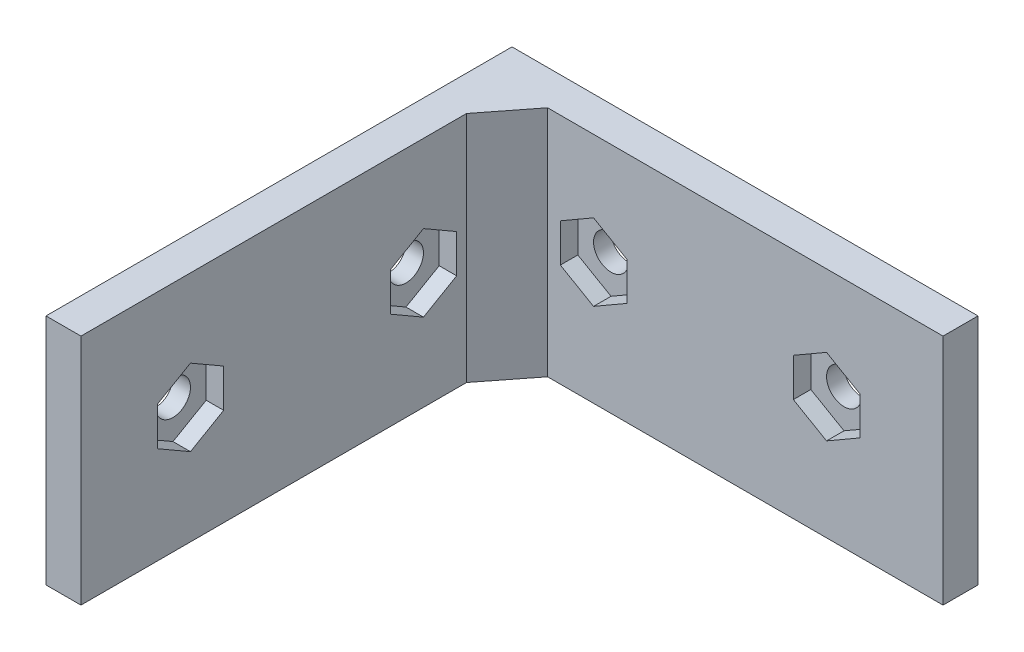
SolidWorks part; units mm, degrees
ref_plane "Plan de face" through (0, 0, 0) normal (0, 0, 1) x (1, 0, 0)
ref_plane "Plan de dessus" through (0, 0, 0) normal (0, 1, 0) x (1, 0, 0)
ref_plane "Plan de droite" through (0, 0, 0) normal (1, 0, 0) x (0, 0, -1)
sketch "Esquisse1" plane through (0, 0, 0) normal (0, 0, 1) x (1, 0, 0)
  line L1 (0, 0) -> (40, 0)
  line L2 (0, 0) -> (0, 20)
  line L3 (0, 20) -> (40, 20)
  line L4 (40, 0) -> (40, 20)
  dimension "D1" = 20
  dimension "D2" = 40
extrude "Boss.-Extru.1" add sketch "Esquisse1" along normal blind 3
sketch "Esquisse2" plane through (0, 0, 3) normal (0, 0, 1) x (1, 0, 0)
  line L0 (0, 20) -> (0, 0) construction
  line L1 (0, 0) -> (40, 0) construction
  circle A0 centre (10, 10.5) radius 1.5
  circle A1 centre (30, 10.5) radius 1.5
  dimension "D1" = 3
  dimension "D2" = 3
  dimension "D4" = 20
  dimension "D5" = 10.5
  dimension "D6" = 10.5
  dimension "D3" = 10
extrude "Enlèv. mat.-Extru.1" cut sketch "Esquisse2" against normal blind 3
sketch "Esquisse3" plane through (0, 0, 3) normal (0, 0, 1) x (1, 0, 0)
  line L0 (0, 0) -> (40, 0) construction
  line L1 (0, 20) -> (3, 20)
  line L2 (0, 20) -> (0, 0)
  line L3 (0, 0) -> (3, 0)
  line L4 (3, 20) -> (3, 0)
  dimension "D1" = 3
extrude "Boss.-Extru.2" add sketch "Esquisse3" along normal blind 37
sketch "Esquisse4" plane through (0, 0, 0) normal (-1, 0, 0) x (0, 0, 1)
  line L0 (0, 20) -> (0, 0) construction
  line L1 (40, 0) -> (0, 0) construction
  circle A0 centre (10.6, 10) radius 1.5
  circle A1 centre (30.6, 10) radius 1.5
  dimension "D1" = 3
  dimension "D2" = 3
  dimension "D3" = 20
  dimension "D4" = 10.6
  dimension "D5" = 10
  dimension "D6" = 10
extrude "Enlèv. mat.-Extru.2" cut sketch "Esquisse4" against normal blind 3
sketch "Esquisse5" plane through (3, 0, 0) normal (1, 0, 0) x (0, 0, -1)
  line L1 (-13.45, 8.3546) -> (-10.6, 6.7091)
  line L2 (-10.6, 6.7091) -> (-7.75, 8.3546)
  line L3 (-7.75, 8.3546) -> (-7.75, 11.6454)
  line L4 (-7.75, 11.6454) -> (-10.6, 13.2909)
  line L5 (-10.6, 13.2909) -> (-13.45, 11.6454)
  line L6 (-13.45, 11.6454) -> (-13.45, 8.3546)
  line L7 (-30.6, 6.7091) -> (-27.75, 8.3546)
  line L8 (-27.75, 8.3546) -> (-27.75, 11.6454)
  line L9 (-27.75, 11.6454) -> (-30.6, 13.2909)
  line L10 (-30.6, 13.2909) -> (-33.45, 11.6454)
  line L11 (-33.45, 11.6454) -> (-33.45, 8.3546)
  line L12 (-33.45, 8.3546) -> (-30.6, 6.7091)
  circle A0 centre (-10.6, 10) radius 2.85 construction
  circle A1 centre (-30.6, 10) radius 2.85 construction
  dimension "D1" = 5.7
  dimension "D2" = 5.7
extrude "Enlèv. mat.-Extru.3" cut sketch "Esquisse5" against normal blind 1.5
sketch "Esquisse6" plane through (0, 0, 3) normal (0, 0, 1) x (1, 0, 0)
  line L1 (27.15, 8.8546) -> (30, 7.2091)
  line L2 (30, 7.2091) -> (32.85, 8.8546)
  line L3 (32.85, 8.8546) -> (32.85, 12.1454)
  line L4 (32.85, 12.1454) -> (30, 13.7909)
  line L5 (30, 13.7909) -> (27.15, 12.1454)
  line L6 (27.15, 12.1454) -> (27.15, 8.8546)
  line L7 (10, 7.2091) -> (12.85, 8.8546)
  line L8 (12.85, 8.8546) -> (12.85, 12.1454)
  line L9 (12.85, 12.1454) -> (10, 13.7909)
  line L10 (10, 13.7909) -> (7.15, 12.1454)
  line L11 (7.15, 12.1454) -> (7.15, 8.8546)
  line L12 (7.15, 8.8546) -> (10, 7.2091)
  circle A0 centre (30, 10.5) radius 2.85 construction
  circle A1 centre (10, 10.5) radius 2.85 construction
  point P10 (31.425, 12.9682)
  dimension "D1" = 5.7
  dimension "D2" = 5.7
extrude "Enlèv. mat.-Extru.4" cut sketch "Esquisse6" against normal blind 1.5
sketch "Esquisse7" plane through (0, 0, 0) normal (0, -1, 0) x (1, 0, 0)
  line L0 (6.0544, 3) -> (3, 6.9046)
  line L1 (3, 3) -> (40, 3) construction
  line L2 (3, 40) -> (3, 3) construction
  line L9 (0, 0) -> (40, 0)
  line L10 (40, 0) -> (40, 3)
  line L11 (40, 3) -> (3, 3)
  line L12 (3, 3) -> (3, 40)
  line L13 (3, 40) -> (0, 40)
  line L14 (0, 40) -> (0, 0)
  line L17 (6.0544, 3) -> (3, 3)
  line L18 (3, 3) -> (3, 6.9046)
  point P6 (3, 6.9046)
  point P7 (6.0544, 3)
  dimension "D1" = 0
extrude "Boss.-Extru.3" add sketch "Esquisse7" against normal blind 20
